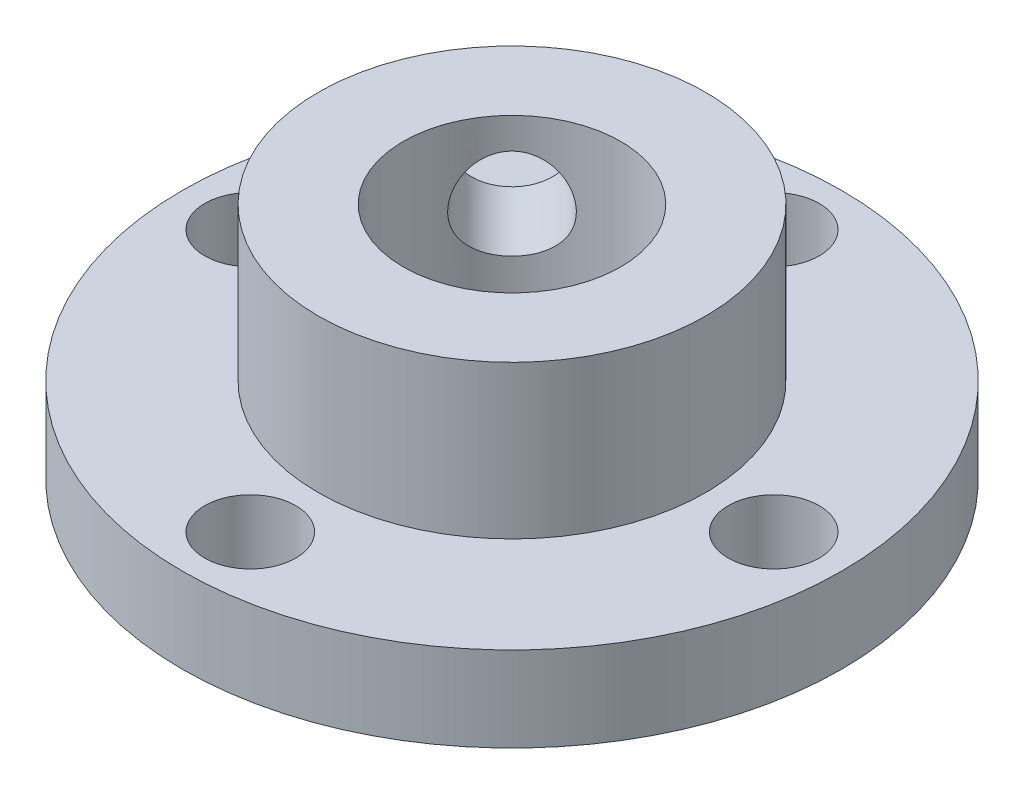
SolidWorks part; units mm, degrees
ref_plane "Front Plane" through (0, 0, 0) normal (0, 0, 1) x (1, 0, 0)
ref_plane "Top Plane" through (0, 0, 0) normal (0, 1, 0) x (1, 0, 0)
ref_plane "Right Plane" through (0, 0, 0) normal (1, 0, 0) x (0, 0, -1)
sketch "Sketch1" plane through (0, 0, 0) normal (0, 1, 0) x (1, 0, 0)
  circle A0 centre (0, 0) radius 4.064
  circle A1 centre (0, 0) radius 7.239
  circle A2 centre (0, 0) radius 12.319
  dimension "D1" = 8.128
  dimension "D2" = 3.175
  dimension "D3" = 5.08
extrude "Boss-Extrude1" add sketch "Sketch1" along normal blind 8.89 contours A1 A0 region at (-7.0343, 0, 0)
extrude "Boss-Extrude2" add sketch "Sketch1<3>" along normal blind 3.175 contours A2 A1 region at (-11.9706, 0, 0)
sketch "Sketch1<3>" plane through (0, 0, 0) normal (0, 1, 0) x (1, 0, 0) same geometry as "Sketch1"
sketch "Sketch2" plane through (0, 3.175, 0) normal (0, 1, 0) x (1, 0, 0)
  line L0 (0, 12.319) -> (0, 7.239) construction
  circle A0 centre (0, 9.779) radius 1.7
  circle A1 centre (9.779, 0) radius 1.7
  circle A2 centre (0, -9.779) radius 1.7
  circle A3 centre (-9.779, 0) radius 1.7
  circle A4 centre (0, 0) radius 12.319 construction
  circle A5 centre (0, 0) radius 7.239 construction
  point P4 (0, 9.779)
  point P11 (0, 0)
  dimension "D1" = 3.4
  dimension "D2" = 4
extrude "Cut-Extrude1" cut sketch "Sketch2" against normal blind 3.175
ref_axis "Axis1" through (0, 0, -9.779) along (0, 1, 0)
ref_axis "Axis2" through (-9.779, 0, 0) along (0, 1, 0)
ref_plane "Plane1" through (-4.8895, 0, -4.8895) normal (-0.7071, 0, -0.7071) x (-0.7071, 0, 0.7071)
sketch "Sketch5" plane through (-4.8895, 0, -4.8895) normal (-0.7071, 0, -0.7071) x (-0.7071, 0, 0.7071)
  line L0 (0, 8.89) -> (0, 3.175) construction
  line L1 (7.239, 8.89) -> (-7.239, 8.89) construction
  line L2 (12.319, 3.175) -> (-12.319, 3.175) construction
  circle A0 centre (0, 6.0325) radius 1.7
  point P10 (0, 6.0325)
  dimension "D1" = 3.4
extrude "Cut-Extrude2" cut sketch "Sketch5" against normal up to next and the other way up to next
sketch "Sketch6" plane through (0, 0, 0) normal (0, 1, 0) x (1, 0, 0)
  circle A0 centre (0, 0) radius 9.779 construction
